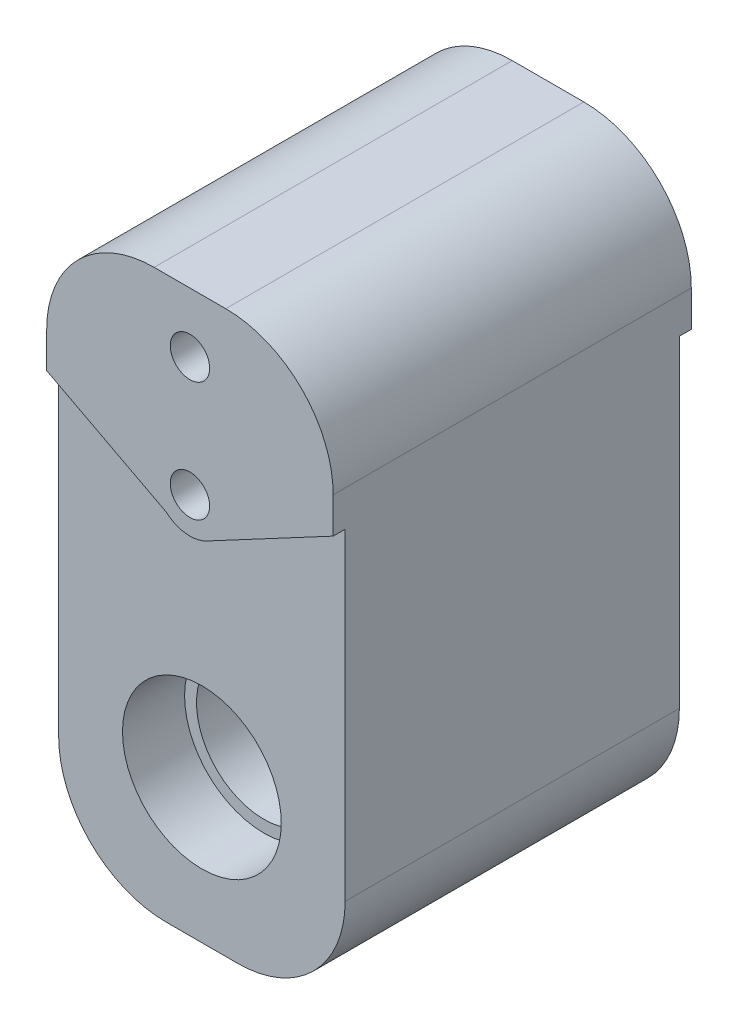
SolidWorks part; units mm, degrees
ref_plane "Спереди" through (0, 0, 0) normal (0, 0, 1) x (1, 0, 0)
ref_plane "Сверху" through (0, 0, 0) normal (0, 1, 0) x (1, 0, 0)
ref_plane "Справа" through (0, 0, 0) normal (1, 0, 0) x (0, 0, -1)
sketch "Эскиз1" plane through (0, 0, 0) normal (0, 0, 1) x (1, 0, 0)
  line L0 (0, 36) -> (0, -12) construction
  line L1 (-12, 36) -> (12, 36)
  line L2 (-12, 36) -> (-12, -12)
  line L3 (-12, -12) -> (12, -12)
  line L4 (12, 36) -> (12, -12)
  line L6 (-12, 0) -> (12, 0) construction
  dimension "D1" = 24
  dimension "D2" = 12
  dimension "D3" = 36
extrude "тело" add sketch "Эскиз1" along normal blind 14 and the other way blind 14
sketch "Эскиз2" plane through (0, 0, 14) normal (0, 0, 1) x (1, 0, 0)
  circle A0 centre (0, 0) radius 6.65
  dimension "D1" = 13.3
extrude "углубление для подшипника" cut sketch "Эскиз2" against normal blind 5.2
sketch "Эскиз4" plane through (0, 0, 8.8) normal (0, 0, 1) x (1, 0, 0)
  line L1 (0, 36) -> (0, -12) construction
  line L2 (-12, 0) -> (12, 0) construction
  circle A0 centre (0, 0) radius 5.65
  circle A1 centre (0, 0) radius 6.65 construction
  point P4 (0, 0)
  point P7 (0, 0)
  point P10 (0, 0)
  dimension "D1" = 1
extrude "сквозное отверстие" cut sketch "Эскиз4" against normal through all
mirror "Зеркальное отражение2" about plane through (0, 0, 0) normal (0, 0, 1) of "углубление для подшипника"
sketch "Эскиз5" plane through (0, 0, -14) normal (0, 0, -1) x (-1, 0, 0)
  line L0 (0, 36) -> (0, -12) construction
  line L1 (-12, 36) -> (12, 36) construction
  line L2 (12, -12) -> (-12, -12) construction
  circle A0 centre (0, 31) radius 1.65
  circle A1 centre (0, 21) radius 1.65
  dimension "D1" = 3.3
  dimension "D2" = 10
  dimension "D3" = 5
extrude "отверстия под болты" cut sketch "Эскиз5" against normal through all
fillet "Скругление1" radius 9 2 edges at (12, -12, 0) (-12, -12, 0)
sketch "Эскиз9" plane through (0, 0, 14) normal (0, 0, 1) x (1, 0, 0)
  line L0 (-12, 36) -> (-12, 24)
  line L1 (-12, 36) -> (-12, -3) construction
  line L2 (-12, 36) -> (12, 36)
  line L3 (-12, 24) -> (-1.9948, 18.7593)
  line L4 (12, 36) -> (12, 24)
  line L5 (12, 24) -> (1.4118, 18.3529)
  line L6 (12, -3) -> (12, 36) construction
  arc A0 (-1.9948, 18.7593) -> (1.4118, 18.3529) centre (0, 21) ccw
  circle A1 centre (0, 21) radius 1.65
  circle A2 centre (0, 31) radius 1.65
  circle A3 centre (0, 31) radius 1.65 construction
  circle A4 centre (0, 21) radius 1.65 construction
  dimension "D1" = 6
  dimension "D2" = 12
extrude "выступы" add sketch "Эскиз9" along normal blind 1
mirror "Зеркальное отражение1" about plane through (0, 0, 0) normal (0, 0, 1) of "выступы"
fillet "Скругление2" radius 9 2 edges at (12, 36, 0) (-12, 36, 0)
